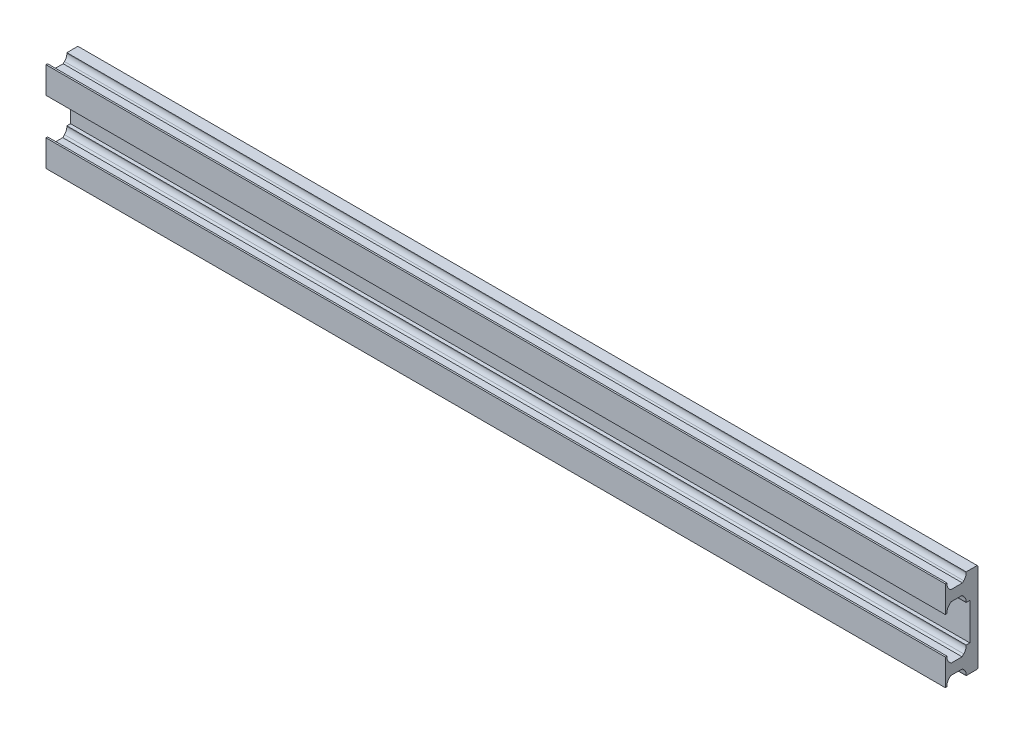
SolidWorks part; units mm, degrees
ref_plane "Front" through (0, 0, 0) normal (0, 0, 1) x (1, 0, 0)
ref_plane "Top" through (0, 0, 0) normal (0, 1, 0) x (1, 0, 0)
ref_plane "Right" through (0, 0, 0) normal (1, 0, 0) x (0, 0, -1)
sketch "Sketch1" plane through (0, 0, 0) normal (0, 0, 1) x (1, 0, 0)
  line L0 (-110, -4) -> (-110, 4) construction
  line L1 (110, 11) -> (-110, 11)
  line L2 (110, 11) -> (110, -11)
  line L3 (110, -11) -> (-110, -11)
  line L4 (-110, 11) -> (-110, -11)
  line L5 (110, 11) -> (-110, -11) construction
  line L6 (110, -11) -> (-110, 11) construction
  line L8 (110, 4) -> (-110, 4) construction
  point P0 (0, 0)
  dimension "D1" = 7
extrude "Boss-Extrude1" add sketch "Sketch1" against normal blind 2
sketch "Sketch2" plane through (0, 0, 0) normal (0, 0, 1) x (1, 0, 0)
  line L0 (-110, 11) -> (-110, -11) construction
  line L1 (110, 11) -> (-110, 11)
  line L2 (110, 11) -> (110, 4.5)
  line L3 (110, 4.5) -> (-110, 4.5)
  line L4 (-110, 11) -> (-110, 4.5)
  line L5 (110, -11) -> (110, 11) construction
  line L6 (110, -11) -> (-110, -11)
  line L7 (110, -11) -> (110, -4.5)
  line L8 (110, -4.5) -> (-110, -4.5)
  line L9 (-110, -11) -> (-110, -4.5)
  line L11 (110, 4) -> (-110, 4) construction
  dimension "D1" = 0.5
extrude "Boss-Extrude2" add sketch "Sketch2" along normal offset from surface (6 mm away) 1
ref_plane "Center of Slots" through (0, 7.75, 0) normal (0, -1, 0) x (-1, 0, 0)
sketch "Sketch5" plane through (0, 0, 0) normal (1, 0, 0) x (0, 0, -1)
  line L16 (-1.9, 6.5) -> (-4.6, 6.5)
  line L17 (-1.9, 6.5) -> (-4.6, 6.5)
  line L18 (-1.4858, 6.0858) -> (-1.9, 6.5)
  line L19 (-1.4858, 6.0858) -> (-1.9, 6.5)
  line L20 (-0.9, 3.8284) -> (-0.9, 4.6716)
  line L21 (-0.9, 3.8284) -> (-0.9, 4.6716)
  line L22 (-1.9, 2) -> (-1.4858, 2.4142)
  line L23 (-1.9, 2) -> (-1.4858, 2.4142)
  line L24 (-4.6, 2) -> (-1.9, 2)
  line L25 (-4.6, 2) -> (-1.9, 2)
  line L26 (-5.0142, 2.4142) -> (-4.6, 2)
  line L27 (-5.0142, 2.4142) -> (-4.6, 2)
  line L28 (-5.6, 4.6716) -> (-5.6, 3.8284)
  line L29 (-5.6, 4.6716) -> (-5.6, 3.8284)
  line L30 (-4.6, 6.5) -> (-5.0142, 6.0858)
  line L31 (-4.6, 6.5) -> (-5.0142, 6.0858)
  arc A12 (-0.9, 4.6716) -> (-1.4858, 6.0858) centre (-2.9, 4.6716) ccw
  arc A13 (-0.9, 4.6716) -> (-1.4858, 6.0858) centre (-2.9, 4.6716) ccw
  arc A14 (-1.4858, 2.4142) -> (-0.9, 3.8284) centre (-2.9, 3.8284) ccw
  arc A15 (-1.4858, 2.4142) -> (-0.9, 3.8284) centre (-2.9, 3.8284) ccw
  arc A16 (-5.6, 3.8284) -> (-5.0142, 2.4142) centre (-3.6, 3.8284) ccw
  arc A17 (-5.6, 3.8284) -> (-5.0142, 2.4142) centre (-3.6, 3.8284) ccw
  arc A18 (-5.0142, 6.0858) -> (-5.6, 4.6716) centre (-3.6, 4.6716) ccw
  arc A19 (-5.0142, 6.0858) -> (-5.6, 4.6716) centre (-3.6, 4.6716) ccw
  dimension "D1" = 0
extrude "Slot 1" cut sketch "Sketch5" against normal through all both and the other way through all
mirror "Slot 1x2" about plane through (0, 7.75, 0) normal (0, -1, 0) of "Slot 1"
mirror "Slot 2" about plane through (0, 0, 0) normal (0, 1, 0) of "Slot 1x2", "Slot 1"
chamfer "Deburs" distance 0.2 angle 45 2 edges at (0, -11, -2) (0, 11, -2)
sketch "Sketch6" plane through (0, 0, 0) normal (1, 0, 0) x (0, 0, -1)
  line L1 (-4.6, 9) -> (-5.0142, 9.4142) construction
  line L2 (-1.4858, 9.4142) -> (-1.9, 9) construction
  line L3 (-4.6, 9) -> (-4.7, 9.1)
  line L4 (-1.8, 9.1) -> (-1.9, 9)
  line L5 (-4.6, 9) -> (-1.9, 9)
  line L6 (-4.7, 9.1) -> (-1.8, 9.1)
  dimension "D1" = 0.1
extrude "Tighten Top Bearing Slot" add sketch "Sketch6" along normal through all and the other way through all
mirror "Tighten Top Bearing Mirror" about plane through (0, 0, 0) normal (0, 1, 0) of "Tighten Top Bearing Slot"
